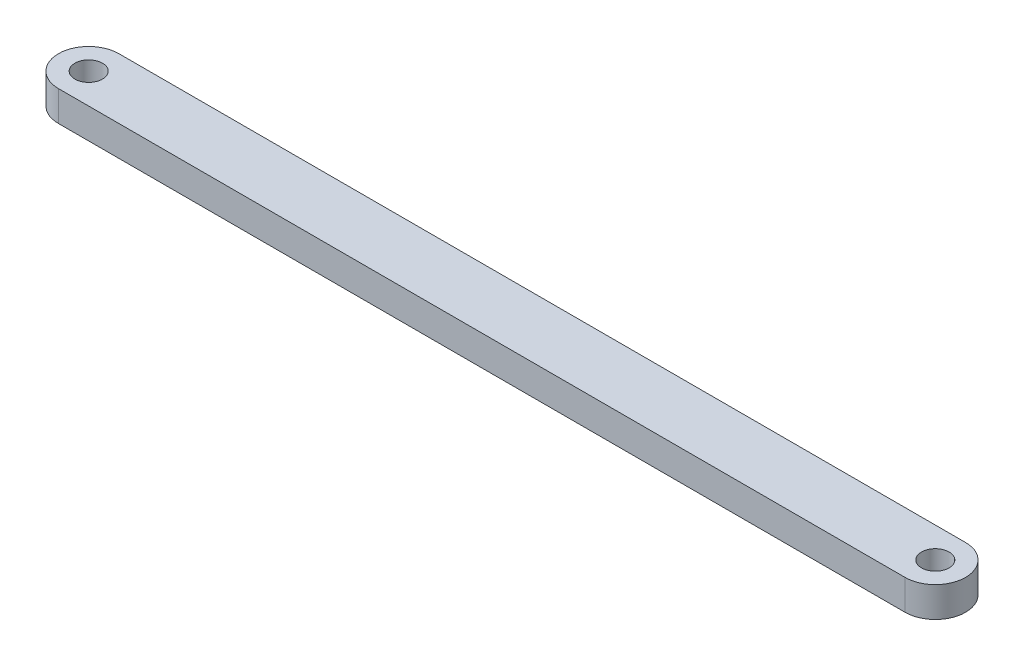
SolidWorks part; units mm, degrees
ref_plane "Front Plane" through (0, 0, 0) normal (0, 0, 1) x (1, 0, 0)
ref_plane "Top Plane" through (0, 0, 0) normal (0, 1, 0) x (1, 0, 0)
ref_plane "Right Plane" through (0, 0, 0) normal (1, 0, 0) x (0, 0, -1)
sketch "Sketch1" plane through (0, 0, 0) normal (0, 1, 0) x (1, 0, 0)
  line L0 (-44.45, 3.175) -> (44.45, 3.175)
  line L1 (-44.45, -3.175) -> (44.45, -3.175)
  circle A0 centre (-44.45, 0) radius 1.45
  circle A1 centre (44.45, 0) radius 1.45
  arc A2 (-44.45, 3.175) -> (-44.45, -3.175) centre (-44.45, 0) ccw
  arc A3 (44.45, 3.175) -> (44.45, -3.175) centre (44.45, 0) cw
  point P4 (0, 0)
  point P10 (44.3378, -3.175)
  dimension "D3" = 2.9
  dimension "D4" = 2.9
  dimension "D5" = 3.175
  dimension "D1" = 88.9
  dimension "D2" = 44.45
extrude "Boss-Extrude1" add sketch "Sketch1" along normal blind 3.175
